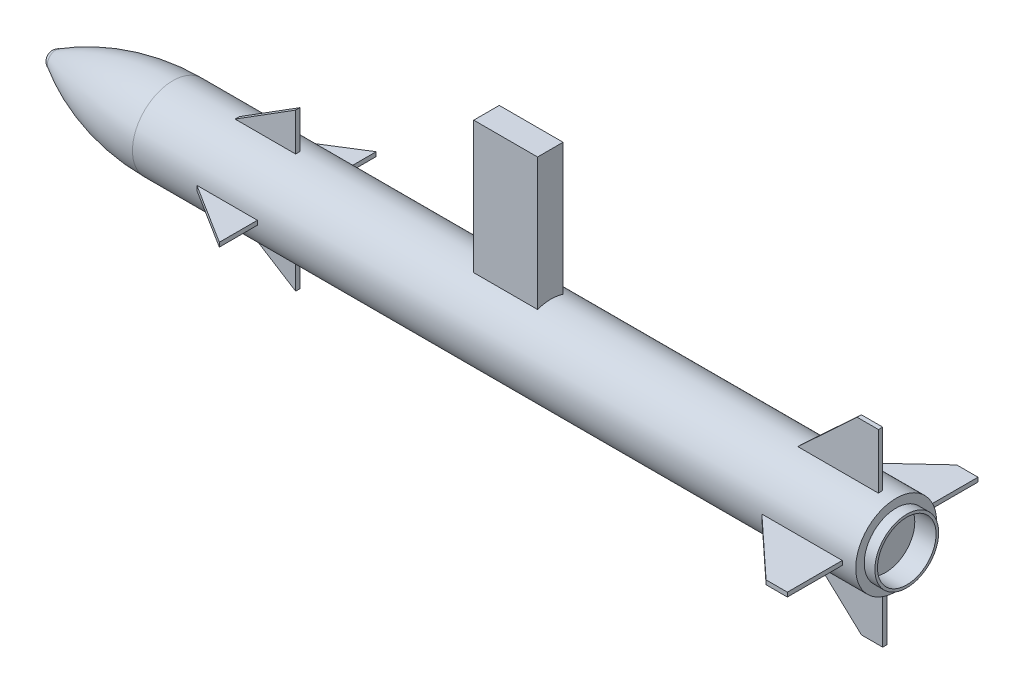
SolidWorks part; units mm, degrees
ref_plane "Plan de face" through (0, 0, 0) normal (0, 0, 1) x (1, 0, 0)
ref_plane "Plan de dessus" through (0, 0, 0) normal (0, 1, 0) x (1, 0, 0)
ref_plane "Plan de droite" through (0, 0, 0) normal (1, 0, 0) x (0, 0, -1)
sketch "Esquisse1" plane through (0, 0, 0) normal (0, 1, 0) x (1, 0, 0)
  line L0 (0, 0) -> (0, 400)
  line L2 (5500, 1900) -> (39500, 1900)
  line L3 (39500, 1900) -> (39500, 1500)
  line L4 (39500, 1500) -> (40000, 1500)
  line L5 (40000, 1500) -> (40000, 0)
  line L6 (40000, 0) -> (0, 0)
  arc A0 (0, 400) -> (5500, 1900) centre (5500, -8933.3333) cw
  dimension "D1" = 40000
  dimension "D2" = 1500
  dimension "D3" = 400
  dimension "D4" = 500
  dimension "D5" = 34000
  dimension "D6" = 400
revolve "Révolution1" add sketch "Esquisse1" angle 360 about L6
dome "Dôme1" faces to dome 1 distance 290 reverse direction no elliptical dome no face at (0, 0, -400) parameters "D1"=290
sketch "Esquisse2" plane through (40000, 0, 0) normal (1, 0, 0) x (0, 0, -1)
  circle A0 centre (0, 0) radius 1377.565
extrude "Enlèv. mat.-Extru.1" cut sketch "Esquisse2" against normal blind 1000
sketch "Esquisse3" plane through (0, 0, 0) normal (0, 0, 1) x (1, 0, 0)
  line L0 (38867.8822, 1693.7552) -> (38867.8822, 4480.7581)
  line L1 (38867.8822, 4480.7581) -> (37867.8822, 4480.7581)
  line L2 (37867.8822, 4480.7581) -> (34867.8822, 1693.7552)
  line L3 (34867.8822, 1693.7552) -> (38867.8822, 1693.7552)
  dimension "D1" = 1000
  dimension "D2" = 4000
extrude "Boss.-Extru.1" add sketch "Esquisse3" along normal blind 200
pattern_circular "Répétition circulaire1" count 4 over 360 about axis through (40000, 0, 0) along (1, 0, 0) of "Boss.-Extru.1"
sketch "Esquisse4" plane through (0, 0, 0) normal (0, 0, 1) x (1, 0, 0)
  line L0 (8155.2795, 1665.2887) -> (11371.991, 3686.4083)
  line L1 (11371.991, 3686.4083) -> (11371.991, 1665.2887)
  line L2 (11371.991, 1665.2887) -> (8155.2795, 1665.2887)
extrude "Boss.-Extru.2" add sketch "Esquisse4" along normal mid plane 200
pattern_circular "Répétition circulaire2" count 4 over 360 about axis through (40000, 0, 0) along (1, 0, 0) of "Boss.-Extru.2"
sketch "Esquisse6" plane through (0, 0, 0) normal (0, 1, 0) x (1, 0, 0)
  line L1 (20279.8933, -636.0873) -> (23279.8933, -636.0873)
  line L2 (20279.8933, -636.0873) -> (20279.8933, 563.9127)
  line L3 (20279.8933, 563.9127) -> (23279.8933, 563.9127)
  line L4 (23279.8933, -636.0873) -> (23279.8933, 563.9127)
  line L5 (20279.8933, -636.0873) -> (23279.8933, 563.9127) construction
  line L6 (20279.8933, 563.9127) -> (23279.8933, -636.0873) construction
  point P0 (21779.8933, -36.0873)
  dimension "D1" = 3000
  dimension "D2" = 1200
extrude "Boss.-Extru.3" add sketch "Esquisse6" along normal blind 8000
scale "Echelle1" scale about centroid uniform scaling yes scale factor 0.05
